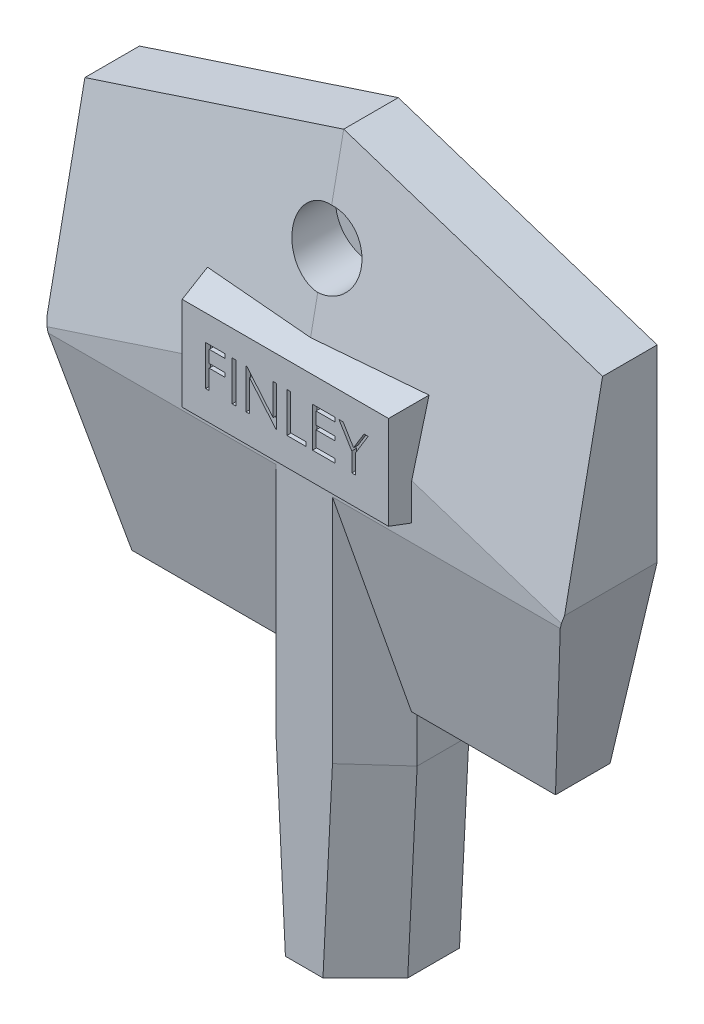
SolidWorks part; units mm, degrees
material "Esun Hard Tough Resin"
ref_plane "Front Plane" through (0, 0, 0) normal (0, 0, 1) x (1, 0, 0)
ref_plane "Top Plane" through (0, 0, 0) normal (0, 1, 0) x (1, 0, 0)
ref_plane "Right Plane" through (0, 0, 0) normal (1, 0, 0) x (0, 0, -1)
sketch "Sketch2" plane through (0, 0, 0) normal (0, 0, 1) x (1, 0, 0)
  line L0 (7.5, 0) -> (27.5, 0)
  line L1 (-27.5, 0) -> (-7.5, 0)
  line L2 (-27.5, 0) -> (-27.5, 50)
  line L3 (-27.5, 50) -> (27.5, 50)
  line L4 (27.5, 0) -> (27.5, 50)
  line L6 (7.5, 0) -> (7.5, -25)
  line L7 (7.5, -25) -> (-7.5, -25)
  line L8 (-7.5, 0) -> (-7.5, -25)
  line L9 (-7.5, 0) -> (7.5, 0) construction
  point P8 (0, 50)
  point P10 (0, -25)
  dimension "D1" = 25
  dimension "D2" = 15
  dimension "D3" = 50
  dimension "D4" = 55
extrude "Boss-Extrude1" add sketch "Sketch2" along normal blind 10
sketch "Sketch3" plane through (0, 0, 10) normal (0, 0, 1) x (1, 0, 0)
  line L0 (-6.5, -25) -> (-7.5, -5)
  line L1 (-7.5, -25) -> (7.5, -25) construction
  line L2 (-7.5, 0) -> (-7.5, -25) construction
  line L3 (-6.5, -25) -> (6.5, -25)
  line L4 (6.5, -25) -> (7.5, -5)
  line L5 (7.5, -25) -> (7.5, 0) construction
  line L6 (7.5, -5) -> (7.5, 0)
  line L7 (-7.5, -5) -> (-7.5, 0)
  line L8 (0, 50) -> (-27.5, 41)
  line L9 (27.5, 50) -> (-27.5, 50) construction
  line L10 (-27.5, 50) -> (-27.5, 0) construction
  line L11 (-27.5, 41) -> (-27.5, 21)
  line L12 (-27.5, 21) -> (-22.5, 0)
  line L13 (-27.5, 0) -> (-7.5, 0) construction
  line L14 (-22.5, 0) -> (-7.5, 0)
  line L15 (0, 50) -> (27.5, 41)
  line L16 (27.5, 0) -> (27.5, 50) construction
  line L17 (27.5, 41) -> (27.5, 21)
  line L19 (27.5, 21) -> (22.5, 0)
  line L20 (7.5, 0) -> (27.5, 0) construction
  line L21 (22.5, 0) -> (7.5, 0)
  point P6 (0, -25)
  dimension "D1" = 13
  dimension "D2" = 5
  dimension "D3" = 9
  dimension "D4" = 20
  dimension "D5" = 15
  dimension "D6" = 15
extrude "Shape cuts" cut sketch "Sketch3" against normal through all flip side to cut
sketch "Sketch4" plane through (0, -25, 0) normal (0, -1, 0) x (1, 0, 0)
  line L0 (-5, 5) -> (5, 5)
  line L1 (5, 5) -> (3, 0)
  line L2 (-6.5, 0) -> (6.5, 0) construction
  line L3 (3, 0) -> (-3, 0)
  line L4 (-3, 0) -> (-5, 5)
  point P7 (0, 5)
  point P8 (0, 0)
  dimension "D1" = 10
  dimension "D2" = 6
  dimension "D3" = 5
extrude "Dove tail" cut sketch "Sketch4" against normal blind 30
sketch "Sketch5" plane through (0, 0, 0) normal (0, 0, -1) x (-1, 0, 0)
  line L0 (3, 5) -> (-3, 5) construction
  circle A0 centre (0, 40) radius 2.05
  point P5 (0, 5)
  dimension "D1" = 4.1
  dimension "D2" = 35
extrude "Fastener" cut sketch "Sketch5" against normal through all
sketch "Sketch7" plane through (0, 0, 10) normal (0, 0, 1) x (1, 0, 0)
  circle A0 centre (0, 40) radius 3.65
  dimension "D1" = 7.3
extrude "Cut-Extrude4" cut sketch "Sketch7" against normal offset from surface (7 mm away) 3 up to face at (-2.05, 40, 0)
sketch "Sketch8" plane through (0, 0, 10) normal (0, 0, 1) x (1, 0, 0)
  line L1 (12, 21) -> (-12, 21)
  line L2 (12, 21) -> (12, 33)
  line L3 (12, 33) -> (-12, 33)
  line L4 (-12, 21) -> (-12, 33)
  line L5 (12, 21) -> (-12, 33) construction
  line L6 (12, 33) -> (-12, 21) construction
  circle A0 centre (0, 40) radius 2.05 construction
  point P0 (0, 27)
  dimension "D1" = 12
  dimension "D2" = 24
  dimension "D3" = 7
extrude "Names Plate" add sketch "Sketch8" along normal blind 2
chamfer "Chamfer1" distance 4.2 angle 78 4 edges at (15, 0, 10) (-15, 0, 10) (-13.75, 45.5, 10) (13.75, 45.5, 10)
chamfer "Chamfer2" distance 4.5 angle 45 2 edges at (7, -15, 10) (-7, -15, 10)
chamfer "Chamfer3" distance 4.5 angle 13 4 edges at (0, 33, 12) (12, 27, 12) (0, 21, 12) (-12, 27, 12)
sketch "Sketch9" plane through (0, 0, 12) normal (0, 0, 1) x (1, 0, 0)
  line L0 (0, 0) -> (0, 25) construction
  line L1 (-9.5, 25) -> (9.5, 25) construction
  text T0 "FINLEY" font "Century Gothic" height in points 16
  point P4 (0, 25)
  dimension "D1" = 25
  dimension "D2" = 19
extrude "AVA name print" cut sketch "Sketch9" against normal blind 0.5
sketch "Sketch10" plane through (0, 0, 12) normal (0, 0, 1) x (1, 0, 0)
  line L0 (0, 31.6062) -> (0, 22.9801) construction
  line L1 (-10.9611, 27) -> (-8.1562, 27) construction
  line L2 (-10.9611, 31.9611) -> (-10.9611, 22.0389) construction
  line L3 (10.9611, 27) -> (8.1562, 27) construction
  line L4 (10.9611, 22.0389) -> (10.9611, 31.9611) construction
  text T0 "KOALBY"
extrude "KOALBY Name Print" [suppressed] cut sketch "Sketch10" against normal blind 0.5
